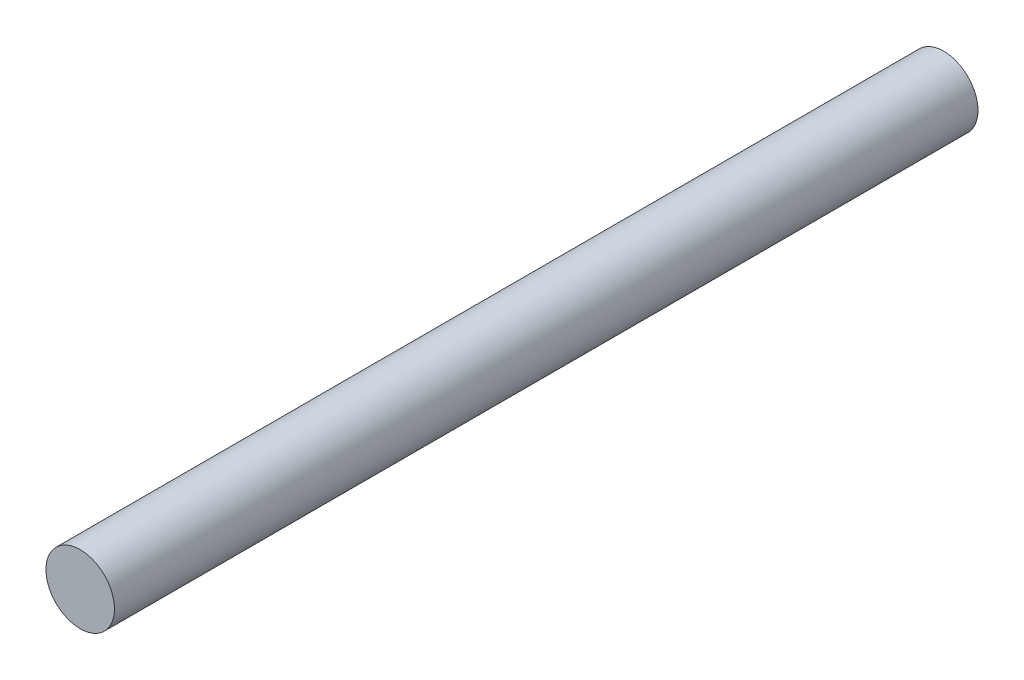
SolidWorks part; units mm, degrees
ref_plane "Front Plane" through (0, 0, 0) normal (0, 0, 1) x (1, 0, 0)
ref_plane "Top Plane" through (0, 0, 0) normal (0, 1, 0) x (1, 0, 0)
ref_plane "Right Plane" through (0, 0, 0) normal (1, 0, 0) x (0, 0, -1)
sketch "Sketch2" plane through (0, 0, 0) normal (0, 0, 1) x (1, 0, 0)
  circle A0 centre (0, 0) radius 0.7937
  dimension "D1" = 1.5875
extrude "Boss-Extrude1" add sketch "Sketch2" along normal blind 20
